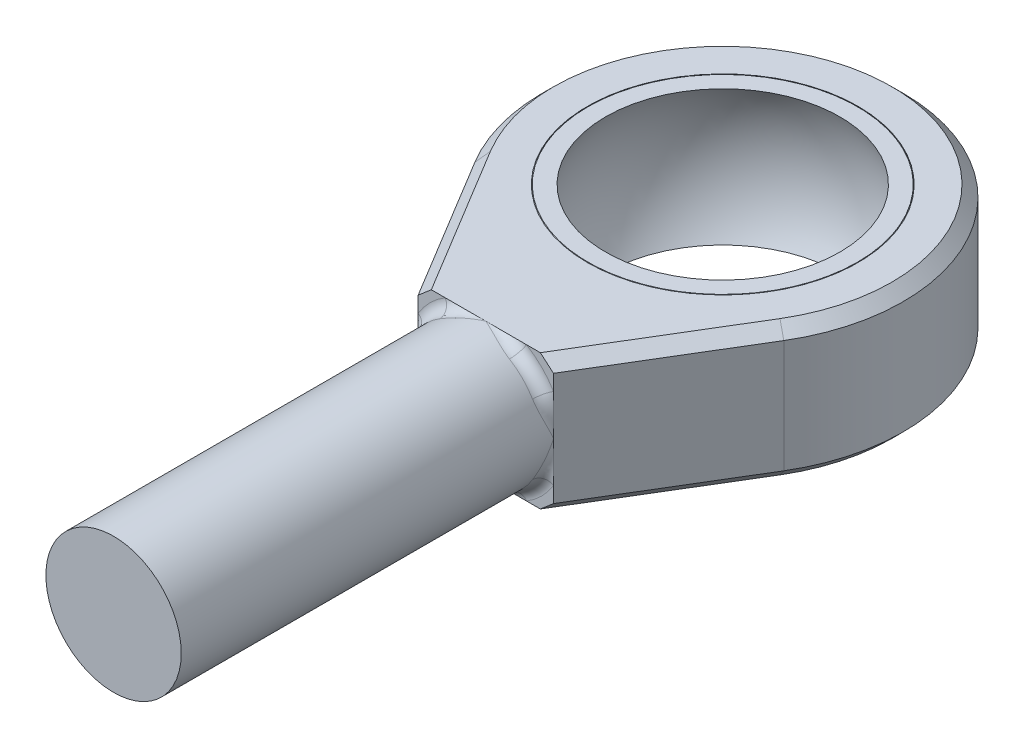
SolidWorks part; units mm, degrees
material "Cast Stainless Steel"
ref_plane "Front Plane" through (0, 0, 0) normal (0, 0, 1) x (1, 0, 0)
ref_plane "Top Plane" through (0, 0, 0) normal (0, 1, 0) x (1, 0, 0)
ref_plane "Right Plane" through (0, 0, 0) normal (1, 0, 0) x (0, 0, -1)
sketch "Sketch1" plane through (0, 0, 0) normal (0, 1, 0) x (1, 0, 0)
  line L0 (-6, -21) -> (-13.6918, -8.2785)
  line L1 (6, -21) -> (-6, -21)
  line L5 (6, -21) -> (13.6918, -8.2785)
  arc A0 (13.6918, -8.2785) -> (-13.6918, -8.2785) centre (0, 0) ccw
  point P7 (0, -21)
  dimension "D1" = 32
  dimension "D2" = 12
  dimension "D3" = 12.7215
extrude "Boss-Extrude1" add sketch "Sketch1" along normal blind 12
chamfer "Chamfer1" distance 1 angle 45 6 edges at (9.8459, 0, 14.6393) (-9.8459, 0, 14.6393) (0, 0, -16) (9.8459, 12, 14.6393) (-9.8459, 12, 14.6393) (0, 12, -16)
sketch "Sketch2" plane through (0, 0, 21) normal (0, 0, 1) x (1, 0, 0)
  circle A0 centre (0, 6) radius 6
  dimension "D1" = 12
extrude "Boss-Extrude2" add sketch "Sketch2" along normal blind 33
cosmetic thread "Cosmetic Thread1" parameters "D2"=10.072
fillet "Fillet2" radius 1 4 edges at (4.2426, 1.7574, 21) (-4.2426, 1.7574, 21) (-4.2426, 10.2426, 21) (4.2426, 10.2426, 21)
sketch "Sketch3" plane through (0, 0, 0) normal (1, 0, 0) x (0, 0, -1)
  line L0 (0, 0) -> (0, 12)
  line L1 (0, 12) -> (12, 12)
  line L2 (15, 12) -> (-7.7611, 12) construction
  line L3 (0, 14.3906) -> (0, -2.6097) construction
  line L4 (-7.7611, 0) -> (15, 0) construction
  line L5 (12, 0) -> (0, 0)
  arc A0 (12, 0) -> (12, 12) centre (4, 6) ccw
  dimension "D1" = 20
  dimension "D2" = 12
  dimension "D3" = 12
revolve "Cut-Revolve1" cut sketch "Sketch3" angle 360 about L3
sketch "Sketch4" plane through (0, 0, 0) normal (0, 0, 1) x (1, 0, 0)
  line L0 (-11.9404, 12) -> (-10.388, 12)
  line L2 (12, 12) -> (-12, 12) construction
  line L3 (-10.3966, 0) -> (-11.9478, 0)
  line L4 (-12, 0) -> (12, 0) construction
  line L5 (0, 14.2454) -> (0, -2.302) construction
  arc A0 (-11.9404, 12) -> (-11.9478, 0) centre (0, 5.9926) ccw
  arc A1 (-10.388, 12) -> (-10.3966, 0) centre (0, 5.9926) ccw
  dimension "D1" = 24
revolve "Revolve1" add sketch "Sketch4" angle 360 about L5
